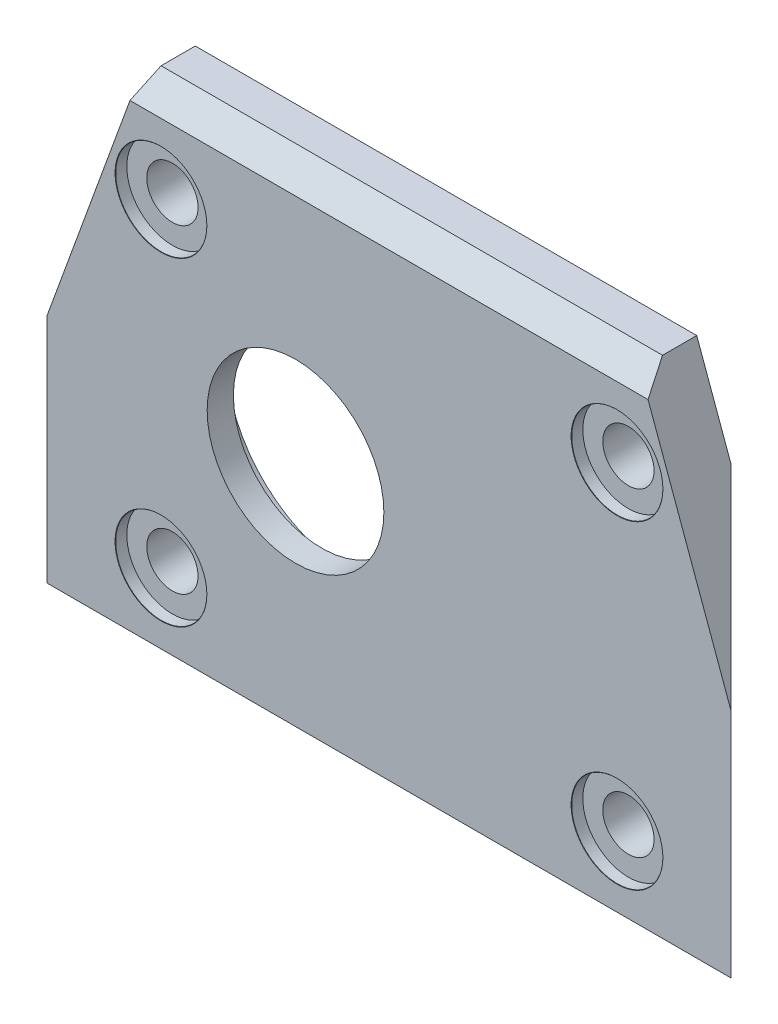
SolidWorks part; units mm, degrees
material "ABS"
ref_plane "Front Plane" through (0, 0, 0) normal (0, 0, 1) x (1, 0, 0)
ref_plane "Top Plane" through (0, 0, 0) normal (0, 1, 0) x (1, 0, 0)
ref_plane "Right Plane" through (0, 0, 0) normal (1, 0, 0) x (0, 0, -1)
sketch "Sketch2" plane through (0, 0, 0) normal (0, 0, 1) x (1, 0, 0)
  line L1 (-30, -22.15) -> (30, -22.15)
  line L2 (-30, -22.15) -> (-30, 22.15)
  line L3 (-30, 22.15) -> (30, 22.15)
  line L4 (30, -22.15) -> (30, 22.15)
  line L5 (-30, -22.15) -> (30, 22.15) construction
  line L6 (-30, 22.15) -> (30, -22.15) construction
  circle A0 centre (-20, 14) radius 2.25
  circle A1 centre (-20, -14) radius 2.25
  circle A2 centre (20, 14) radius 2.25
  circle A3 centre (20, -14) radius 2.25
  circle A4 centre (-8.2, 0) radius 7.75
  point P0 (0, 0)
  dimension "D7" = 4.5
  dimension "D8" = 4.5
  dimension "D9" = 4.5
  dimension "D10" = 4.5
  dimension "D11" = 15.5
  dimension "D1" = 60
  dimension "D2" = 22.15
  dimension "D3" = 40
  dimension "D4" = 28
  dimension "D5" = 20
  dimension "D6" = 14
  dimension "D12" = 11.8
extrude "Boss-Extrude1" add sketch "Sketch2" along normal blind 5
hole_wizard "CBORE for M4 Hex Socket Head Cap Screw1" positions "Sketch6" profile "Sketch4" counterbore size "M4" standard "DIN" end condition up to next
sketch "Sketch6" plane through (0, 0, 5) normal (0, 0, 1) x (1, 0, 0)
  point P0 (-20, 14)
  point P3 (20, 14)
  point P6 (20, -14)
  point P9 (-20, -14)
sketch "Sketch4" plane through (-20, 14, 5) normal (1, 0, 0) x (0, -1, 0)
  line L0 (0, 0) -> (0, 5)
  line L1 (0, 5) -> (2.25, 5)
  line L3 (2.25, 5) -> (2.25, 1)
  line L4 (4, 1) -> (2.25, 1)
  line L5 (4, 1) -> (4, 0.025)
  line L6 (4, 0.025) -> (4.025, 0)
  line L7 (4.025, 0) -> (0, 0)
  line L8 (-4, 0.025) -> (-4.025, 0) construction
  line L11 (0, -6.35) -> (0, 107.95) construction
  dimension "Thru Hole Dia." = 4.5
  dimension "Thru Hole Depth" = 5
  dimension "C'Bore Dia." = 8
  dimension "C'Bore Depth" = 1
  dimension "Near C'Sink Dia." = 8.05
  dimension "Near C'Sink Angle" = 90
sketch "Sketch7" plane through (0, 0, 0) normal (0, 0, -1) x (-1, 0, 0)
  circle A0 centre (8.2, 0) radius 11.1
  dimension "D1" = 22.2
extrude "Cut-Extrude1" cut sketch "Sketch7" against normal blind 2.7
chamfer "Chamfer2" distance 22 angle 20 2 edges at (30, 22.15, 2.5) (-30, 22.15, 2.5) first distance on face at (30, 0, 2.5) first distance on face at (-30, 0, 2.5)
chamfer "Chamfer3" distance 2 angle 45 2 edges at (0, 22.15, 5) (0, -22.15, 5)
chamfer "Chamfer1" distance 5 angle 45 2 edges at (-30, -11, 0) (30, -11, 0)
